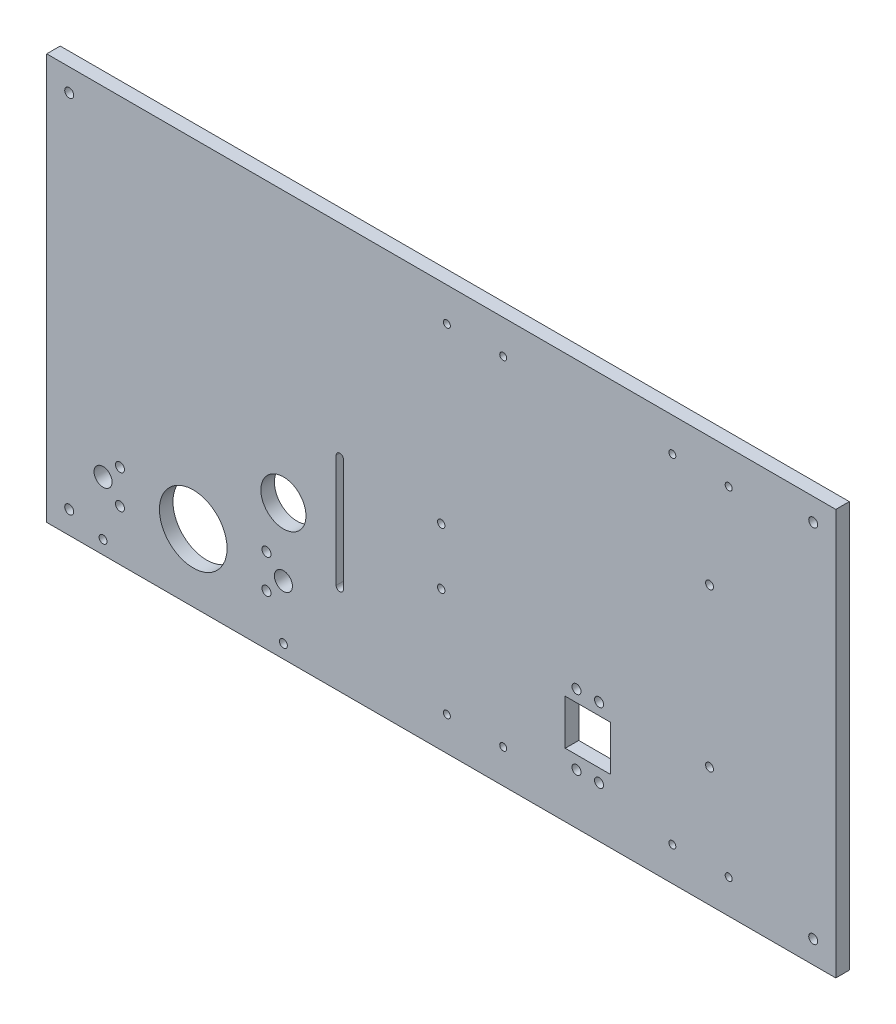
SolidWorks part; units mm, degrees
material "Balsa"
ref_plane "Plano frontal" through (0, 0, 0) normal (0, 0, 1) x (1, 0, 0)
ref_plane "Plano superior" through (0, 0, 0) normal (0, 1, 0) x (1, 0, 0)
ref_plane "Plano direito" through (0, 0, 0) normal (1, 0, 0) x (0, 0, -1)
sketch "Esboço1" plane through (0, 0, 0) normal (0, 0, 1) x (1, 0, 0)
  line L0 (175, 0) -> (-175, 0) construction
  line L1 (-175, 90) -> (175, 90)
  line L2 (-175, 90) -> (-175, -90)
  line L3 (-175, -90) -> (175, -90)
  line L4 (175, 90) -> (175, -90)
  line L5 (-175, 90) -> (175, -90) construction
  line L6 (-175, -90) -> (175, 90) construction
  line L8 (-118.2276, -60) -> (-99.3617, -60) construction
  line L9 (25, 5) -> (25, -80) construction
  line L10 (105, 5) -> (25, 5) construction
  line L11 (25, -80) -> (105, -80) construction
  line L12 (-110, -54.1086) -> (-110, -81.356) construction
  line L13 (55, -41.75) -> (75, -41.75)
  line L14 (55, -41.75) -> (55, -61.75)
  line L15 (55, -61.75) -> (75, -61.75)
  line L16 (75, -41.75) -> (75, -61.75)
  line L17 (55, -41.75) -> (75, -61.75) construction
  line L18 (55, -61.75) -> (75, -41.75) construction
  line L26 (95, 0) -> (-255, 0) construction
  circle A0 centre (105, 5) radius 1.5 construction
  circle A1 centre (105, -80) radius 1.5 construction
  circle A2 centre (25, -80) radius 1.5 construction
  circle A3 centre (25, 5) radius 1.5 construction
  circle A4 centre (-142.5, -52.5) radius 2
  circle A5 centre (-77.5, -52.5) radius 2
  circle A6 centre (-110, -60) radius 15
  circle A7 centre (-70, -60) radius 4
  circle A8 centre (-150, -60) radius 4
  circle A9 centre (-77.5, -67.5) radius 2
  circle A10 centre (-142.5, -67.5) radius 2
  circle A11 centre (0, -3) radius 1.65
  circle A12 centre (0, -28) radius 1.65
  point P0 (0, 0)
  point P21 (5, 0)
  point P23 (65, -51.75)
  point P28 (65, -80)
  dimension "D5" = 3
  dimension "D8" = 32.5
  dimension "D16" = 30
  dimension "D19" = 8
  dimension "D20" = 80
  dimension "D10" = 4
  dimension "D21" = 3.3
  dimension "D1" = 350
  dimension "D2" = 180
  dimension "D3" = 70
  dimension "D4" = 85
  dimension "D7" = 80
  dimension "D9" = 15
  dimension "D11" = 25
  dimension "D12" = 10
  dimension "D13" = 20
  dimension "D14" = 20
  dimension "D15" = 28.25
  dimension "D17" = 65
  dimension "D18" = 30
  dimension "D22" = 25
  dimension "D23" = 8
  dimension "D6" = 2
extrude "Ressalto-extrusão1" add sketch "Esboço1" along normal blind 6 contours L4 L1 L2 L3 A3 A1 A0 A2 region at (1.1072, 1.1733, 0)
sketch "Esboço2" plane through (0, 0, 6) normal (0, 0, 1) x (1, 0, 0)
  line L0 (175, 0) -> (-175, 0) construction
  line L1 (-175, 90) -> (175, 90)
  line L2 (-175, 90) -> (-175, -90)
  line L3 (-175, -90) -> (175, -90)
  line L4 (175, 90) -> (175, -90)
  line L5 (-175, 90) -> (175, -90) construction
  line L6 (-175, -90) -> (175, 90) construction
  line L7 (165, 80) -> (165, 90) construction
  line L8 (165, -80) -> (165, -90) construction
  line L9 (-175, 90) -> (175, 90) construction
  circle A0 centre (165, -80) radius 2
  circle A1 centre (165, 80) radius 2
  circle A2 centre (-165, 80) radius 2
  circle A3 centre (-165, -80) radius 2
  point P0 (0, 0)
  point P16 (0.5357, 0)
  dimension "D3" = 4
  dimension "D2" = 180
  dimension "D4" = 10
  dimension "D5" = 10
  dimension "D6" = 10
  dimension "D7" = 10
extrude "espacador" cut sketch "Esboço2" against normal blind 10 contours A2 | A1 | A0 | A3 region at (165, -80, 6) region at (165, 80, 6) region at (-165, 80, 6) region at (-165, -80, 6)
sketch "Esboço3" plane through (0, 0, 6) normal (0, 0, 1) x (1, 0, 0)
  line L1 (-175, -90) -> (175, -90) construction
  line L2 (60, -67.5) -> (70, -67.5) construction
  line L3 (55, -61.75) -> (75, -61.75) construction
  circle A0 centre (70, -67.5) radius 2
  circle A1 centre (70, -36.5) radius 2
  circle A2 centre (60, -36.5) radius 2
  circle A3 centre (60, -67.5) radius 2
  point P2 (65, -67.5)
  point P13 (65, -61.75)
  dimension "D2" = 4
  dimension "D3" = 22.5
  dimension "D4" = 31
  dimension "D5" = 10
extrude "Corte-extrusão2" cut sketch "Esboço3" against normal blind 10
sketch "Esboço4" plane through (0, 0, 6) normal (0, 0, 1) x (1, 0, 0)
  line L0 (102.5, 75) -> (127.5, 75) construction
  line L1 (2.5, 75) -> (27.5, 75) construction
  line L2 (65, -41.75) -> (65, 53.8452) construction
  line L3 (55, -41.75) -> (75, -41.75) construction
  line L4 (127.5, -75) -> (102.5, -75) construction
  line L5 (2.5, -75) -> (27.5, -75) construction
  line L6 (175, 0) -> (131.6351, 0) construction
  line L7 (175, 90) -> (175, -90) construction
  circle A0 centre (102.5, 75) radius 1.55
  circle A1 centre (127.5, 75) radius 1.55
  circle A2 centre (2.5, 75) radius 1.55
  circle A3 centre (27.5, 75) radius 1.55
  circle A4 centre (127.5, -75) radius 1.55
  circle A5 centre (102.5, -75) radius 1.55
  circle A6 centre (2.5, -75) radius 1.55
  circle A7 centre (27.5, -75) radius 1.55
  point P8 (15, 75)
  point P9 (115, 75)
  point P22 (15, -75)
  point P23 (115, -75)
  dimension "D2" = 3.1
  dimension "D4" = 3.1
  dimension "D1" = 25
  dimension "D3" = 150
  dimension "D5" = 100
extrude "Corte-extrusão3" cut sketch "Esboço4" against normal blind 10
sketch "Esboço5" plane through (0, 0, 6) normal (0, 0, 1) x (1, 0, 0)
  line L0 (-175, -90) -> (175, -90) construction
  line L1 (-175, 90) -> (-175, -90) construction
  circle A0 centre (-70, -30) radius 10
  dimension "D1" = 20
  dimension "D2" = 60
  dimension "D3" = 105
extrude "fios" cut sketch "Esboço5" against normal blind 10
sketch "Esboço6" plane through (0, 0, 6) normal (0, 0, 1) x (1, 0, 0)
  line L0 (119, -37) -> (119, 33) construction
  line L1 (175, 90) -> (175, -90) construction
  line L2 (-175, 90) -> (175, 90) construction
  circle A0 centre (119, -37) radius 1.75
  circle A1 centre (119, 33) radius 1.75
  dimension "D2" = 3.5
  dimension "D1" = 70
  dimension "D3" = 56
  dimension "D4" = 57
extrude "Corte-extrusão5" cut sketch "Esboço6" against normal blind 10
sketch "Esboço7" plane through (0, 0, 6) normal (0, 0, 1) x (1, 0, 0)
  line L0 (-150, -84) -> (-70, -84) construction
  line L1 (-175, -90) -> (175, -90) construction
  circle A0 centre (-70, -84) radius 1.75
  circle A1 centre (-150, -84) radius 1.75
  circle A3 centre (-150, -60) radius 4 construction
  dimension "D1" = 80
  dimension "D2" = 0
  dimension "D4" = 3.5
  dimension "D3" = 6
extrude "Corte-extrusão6" cut sketch "Esboço7" against normal blind 10
sketch "Esboço8" plane through (0, 0, 6) normal (0, 0, 1) x (1, 0, 0)
  line L0 (-45, -50) -> (-45, 0) construction
  line L1 (-46.6, -50) -> (-46.6, 0)
  line L2 (-43.4, -50) -> (-43.4, 0)
  line L3 (-175, -90) -> (175, -90) construction
  line L4 (-175, 90) -> (-175, -90) construction
  arc A0 (-46.6, -50) -> (-43.4, -50) centre (-45, -50) ccw
  arc A1 (-43.4, 0) -> (-46.6, 0) centre (-45, 0) ccw
  point P2 (-45, -25)
  dimension "D2" = 1.6
  dimension "D1" = 50
  dimension "D3" = 40
  dimension "D4" = 130
extrude "Corte-extrusão7" cut sketch "Esboço8" against normal blind 10
